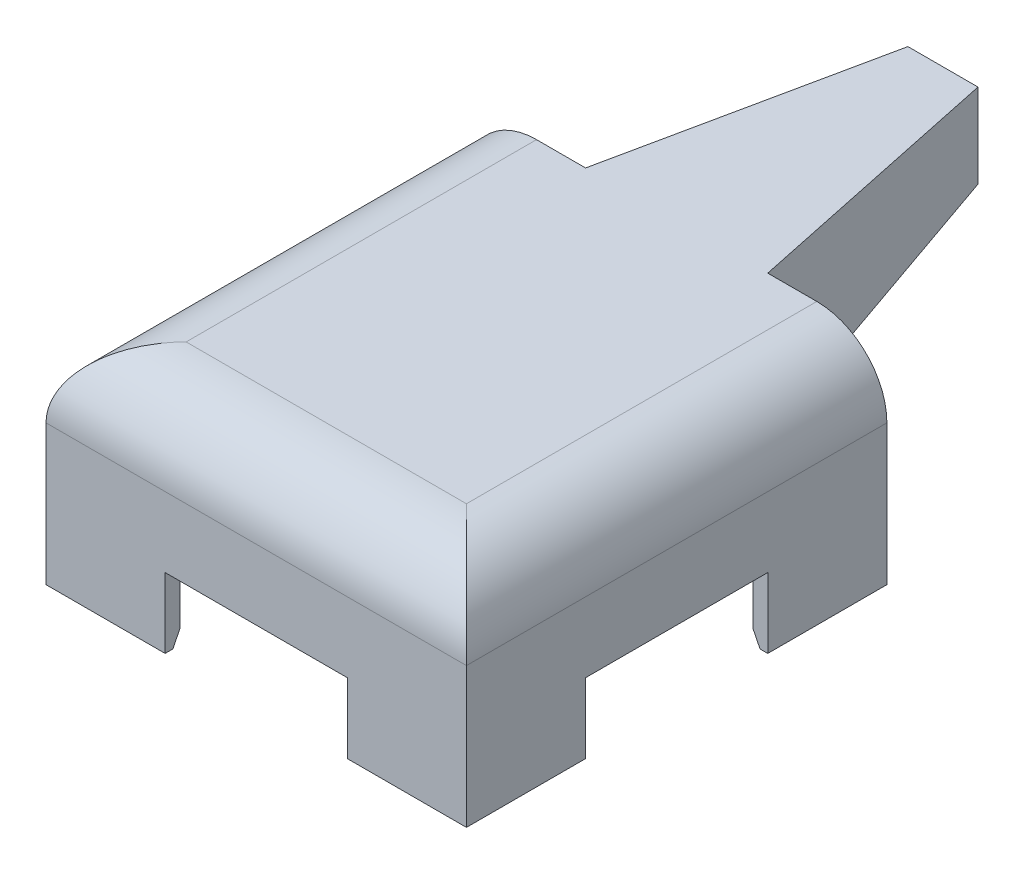
SolidWorks part; units mm, degrees
ref_plane "Front Plane" through (0, 0, 0) normal (0, 0, 1) x (1, 0, 0)
ref_plane "Top Plane" through (0, 0, 0) normal (0, 1, 0) x (1, 0, 0)
ref_plane "Right Plane" through (0, 0, 0) normal (1, 0, 0) x (0, 0, -1)
sketch "Sketch1" plane through (0, 1478.6171, 0) normal (0, 1, 0) x (1, 0, 0)
  line L1 (-530.1492, -768.8296) -> (-453.9492, -768.8296)
  line L2 (-530.1492, -768.8296) -> (-530.1492, -845.0296)
  line L3 (-530.1492, -845.0296) -> (-453.9492, -845.0296)
  line L4 (-453.9492, -768.8296) -> (-453.9492, -845.0296)
  line L5 (-530.1492, -768.8296) -> (-453.9492, -845.0296) construction
  line L6 (-530.1492, -845.0296) -> (-453.9492, -768.8296) construction
  point P0 (-492.0492, -806.9296)
  dimension "D1" = 76.2
  dimension "D2" = 76.2
extrude "Boss-Extrude1" add sketch "Sketch1" along normal blind 25.4
sketch "Sketch2" plane through (0, 1478.6171, 0) normal (0, -1, 0) x (-1, 0, 0)
  line L1 (463.4742, -778.3546) -> (520.6242, -778.3546)
  line L2 (463.4742, -778.3546) -> (463.4742, -835.5046)
  line L3 (463.4742, -835.5046) -> (520.6242, -835.5046)
  line L4 (520.6242, -778.3546) -> (520.6242, -835.5046)
  line L5 (463.4742, -778.3546) -> (520.6242, -835.5046) construction
  line L6 (463.4742, -835.5046) -> (520.6242, -778.3546) construction
  point P0 (492.0492, -806.9296)
  dimension "D1" = 57.15
  dimension "D2" = 57.15
extrude "Cut-Extrude1" cut sketch "Sketch2" against normal blind 19.05
sketch "Sketch3" plane through (0, 1478.6171, 0) normal (0, -1, 0) x (-1, 0, 0)
  line L0 (530.1492, -768.8296) -> (530.1492, -845.0296) construction
  line L1 (530.1492, -790.4196) -> (527.4822, -790.4196)
  line L3 (530.1492, -823.4396) -> (527.4822, -823.4396)
  line L5 (453.9492, -768.8296) -> (530.1492, -768.8296) construction
  line L7 (508.5592, -768.8296) -> (508.5592, -771.4966)
  line L9 (475.5392, -768.8296) -> (475.5392, -771.4966)
  line L10 (530.1492, -845.0296) -> (453.9492, -845.0296) construction
  line L12 (508.5592, -845.0296) -> (508.5592, -842.3626)
  line L14 (475.5392, -845.0296) -> (475.5392, -842.3626)
  line L15 (453.9492, -845.0296) -> (453.9492, -768.8296) construction
  line L16 (453.9492, -823.4396) -> (456.6162, -823.4396)
  line L18 (453.9492, -790.4196) -> (456.6162, -790.4196)
  line L24 (530.1492, -790.4196) -> (530.1492, -768.8296)
  line L25 (530.1492, -768.8296) -> (508.5592, -768.8296)
  line L26 (508.5592, -771.4966) -> (527.4822, -771.4966)
  line L27 (527.4822, -771.4966) -> (527.4822, -790.4196)
  line L28 (530.1492, -823.4396) -> (530.1492, -845.0296)
  line L29 (530.1492, -845.0296) -> (508.5592, -845.0296)
  line L30 (508.5592, -842.3626) -> (527.4822, -842.3626)
  line L31 (527.4822, -842.3626) -> (527.4822, -823.4396)
  line L32 (475.5392, -845.0296) -> (453.9492, -845.0296)
  line L33 (453.9492, -845.0296) -> (453.9492, -823.4396)
  line L34 (475.5392, -842.3626) -> (456.6162, -842.3626)
  line L35 (456.6162, -842.3626) -> (456.6162, -823.4396)
  line L36 (453.9492, -790.4196) -> (453.9492, -768.8296)
  line L37 (453.9492, -768.8296) -> (475.5392, -768.8296)
  line L38 (475.5392, -771.4966) -> (456.6162, -771.4966)
  line L39 (456.6162, -771.4966) -> (456.6162, -790.4196)
  dimension "D1" = 21.59
  dimension "D2" = 21.59
  dimension "D3" = 21.59
  dimension "D4" = 21.59
  dimension "D5" = 21.59
  dimension "D6" = 21.59
  dimension "D7" = 21.59
  dimension "D8" = 21.59
extrude "Boss-Extrude2" add sketch "Sketch3" along normal blind 12.7
chamfer "Chamfer1" distance 2.54 distance2 1.27 8 edges at (-527.4822, 1465.9171, 780.9581) (-518.0207, 1465.9171, 771.4966) (-466.0777, 1465.9171, 771.4966) (-456.6162, 1465.9171, 780.9581) (-456.6162, 1465.9171, 832.9011) (-466.0777, 1465.9171, 842.3626) (-527.4822, 1465.9171, 832.9011) (-518.0207, 1465.9171, 842.3626) first distance on face at (-527.4822, 1472.2671, 780.9581) first distance on face at (-518.0207, 1472.2671, 771.4966) first distance on face at (-466.0777, 1472.2671, 771.4966) first distance on face at (-456.6162, 1472.2671, 780.9581) first distance on face at (-456.6162, 1472.2671, 832.9011) first distance on face at (-466.0777, 1472.2671, 842.3626) first distance on face at (-527.4822, 1472.2671, 832.9011) first distance on face at (-518.0207, 1472.2671, 842.3626)
fillet "Fillet1" radius 12.7 3 edges at (-492.0492, 1504.0171, 845.0296) (-453.9492, 1504.0171, 806.9296) (-530.1492, 1504.0171, 806.9296)
sketch "Sketch4" plane through (0, 0, 768.8296) normal (0, 0, -1) x (-1, 0, 0)
  line L0 (466.6492, 1504.0171) -> (517.4492, 1504.0171) construction
  line L1 (475.5392, 1478.6171) -> (508.5592, 1478.6171)
  line L2 (475.5392, 1478.6171) -> (475.5392, 1504.0171)
  line L3 (475.5392, 1504.0171) -> (508.5592, 1504.0171)
  line L4 (508.5592, 1478.6171) -> (508.5592, 1504.0171)
  dimension "D1" = 0
extrude "Boss-Extrude3" add sketch "Sketch4" along normal blind 48.26
chamfer "Chamfer2" distance 48.26 distance2 10.16 3 edges at (-508.5592, 1491.3171, 720.5696) (-492.0492, 1478.6171, 720.5696) (-475.5392, 1491.3171, 720.5696) first distance on face at (-508.5592, 1491.3171, 744.6996) first distance on face at (-492.0492, 1478.6171, 806.9296) first distance on face at (-475.5392, 1491.3171, 744.6996)
